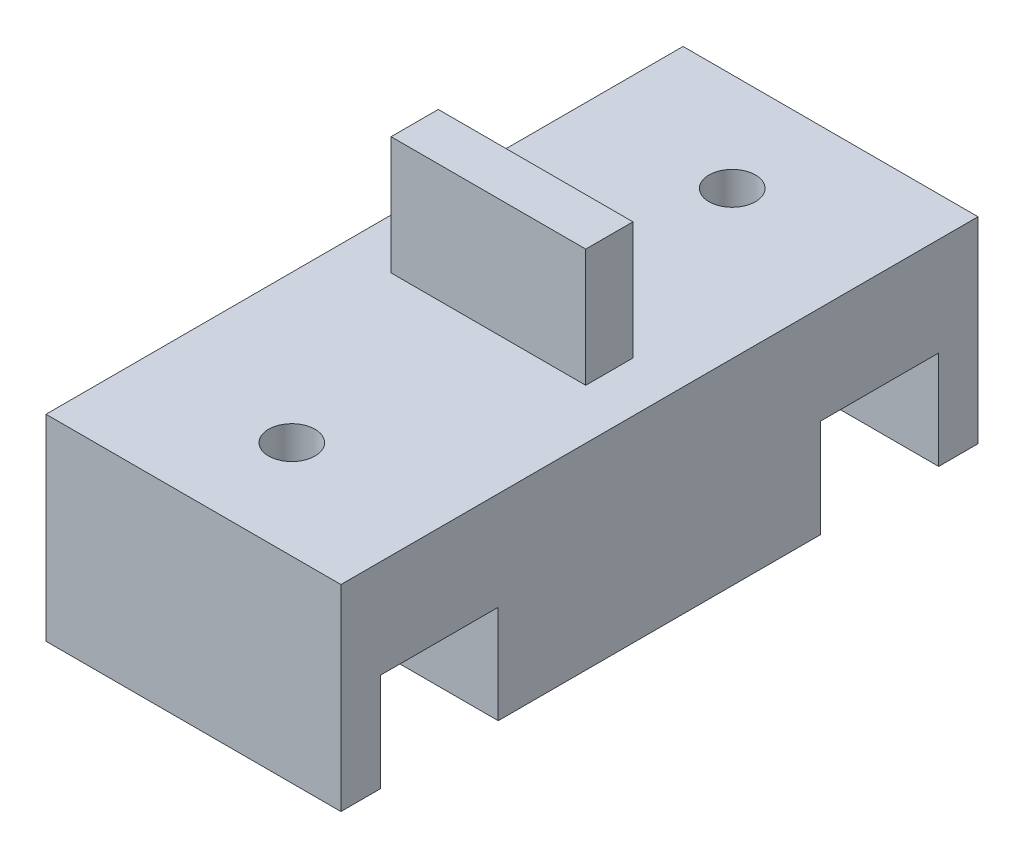
SolidWorks part; units mm, degrees
ref_plane "Front Plane" through (0, 0, 0) normal (0, 0, 1) x (1, 0, 0)
ref_plane "Top Plane" through (0, 0, 0) normal (0, 1, 0) x (1, 0, 0)
ref_plane "Right Plane" through (0, 0, 0) normal (1, 0, 0) x (0, 0, -1)
sketch "Sketch1" plane through (0, 0, 0) normal (1, 0, 0) x (0, 0, -1)
  line L1 (-20.574, 12.7) -> (20.574, 12.7)
  line L2 (-20.574, 12.7) -> (-20.574, 0)
  line L3 (-20.574, 0) -> (20.574, 0)
  line L4 (20.574, 12.7) -> (20.574, 0)
  line L5 (-1.524, 12.7) -> (1.524, 12.7)
  line L6 (-1.524, 12.7) -> (-1.524, 20.32)
  line L7 (-1.524, 20.32) -> (1.524, 20.32)
  line L8 (1.524, 12.7) -> (1.524, 20.32)
  point P10 (0, 20.32)
  point P14 (0, 0)
  dimension "D1" = 12.7
  dimension "D2" = 7.62
  dimension "D3" = 3.048
  dimension "D4" = 19.05
extrude "Boss-Extrude1" add sketch "Sketch1" along normal mid plane 19.05 contours L4 L1 L2 L3 region at (0, 6.35, 0)
extrude "Boss-Extrude2" add sketch "Sketch1<3>" along normal mid plane 12.573 contours L1 L8 L7 L6 region at (0, 16.51, 0)
sketch "Sketch1<3>" plane through (0, 0, 0) normal (1, 0, 0) x (0, 0, -1) same geometry as "Sketch1"
sketch "Sketch2" plane through (0, 0, 1.524) normal (0, 0, 1) x (1, 0, 0)
  line L0 (-6.2865, 19.05) -> (6.2865, 19.05) construction
  line L1 (-6.2865, 12.7) -> (-6.2865, 20.32) construction
  line L2 (6.2865, 12.7) -> (6.2865, 20.32) construction
  line L3 (9.525, 12.7) -> (-9.525, 12.7) construction
  circle A0 centre (0, 31.75) radius 1.5
  point P11 (0, 19.05)
  dimension "D3" = 3
  dimension "D1" = 6.35
  dimension "D2" = 12.7
extrude "Cut-Extrude1" [suppressed] cut sketch "Sketch2" against normal through all
sketch "Sketch4" plane through (0, 12.7, 0) normal (0, 1, 0) x (1, 0, 0)
  line L0 (0, -14.224) -> (0, 14.224) construction
  line L1 (6.2865, -1.524) -> (-6.2865, -1.524) construction
  circle A0 centre (0, -14.224) radius 1.5
  circle A2 centre (0, 14.224) radius 1.5
  point P2 (0, 0)
  dimension "D1" = 3
  dimension "D2" = 12.7
extrude "Cut-Extrude3" cut sketch "Sketch4" against normal through all
sketch "Sketch5" plane through (0, 0, 0) normal (0, -1, 0) x (1, 0, 0)
  line L0 (9.525, -18.034) -> (-9.525, -18.034)
  line L1 (9.525, 20.574) -> (9.525, -20.574) construction
  line L2 (-9.525, 20.574) -> (-9.525, -20.574) construction
  line L3 (-9.525, -18.034) -> (-9.525, -10.414)
  line L4 (-9.525, -10.414) -> (9.525, -10.414)
  line L5 (9.525, -10.414) -> (9.525, -18.034)
  line L6 (-9.525, 10.414) -> (9.525, 10.414)
  line L7 (9.525, 10.414) -> (9.525, 18.034)
  line L8 (9.525, 18.034) -> (-9.525, 18.034)
  line L9 (-9.525, 18.034) -> (-9.525, 10.414)
  circle A0 centre (0, 14.224) radius 3.81
  circle A1 centre (0, -14.224) radius 3.81
  circle A2 centre (0, 14.224) radius 1.5 construction
  circle A3 centre (0, -14.224) radius 1.5 construction
  circle M7 centre (0, 14.224) radius 1.5
  circle M8 centre (0, -14.224) radius 1.5
  line M9 (-9.525, 20.574) -> (-9.525, -20.574)
  line M11 (9.525, -20.574) -> (9.525, 20.574)
  dimension "D1" = 7.62
extrude "Cut-Extrude4" cut sketch "Sketch5" against normal blind 6.35 contours A1 L4 L0 M9 | A1 M8 | A1 L0 L4 M11 | A0 L6 L8 M11 | A0 M7 | A0 L8 L6 M9 region at (6.2033, 0, -14.224) region at (-6.2033, 0, -14.224) region at (-3.7022, 0, -14.224) region at (6.2033, 0, 14.224) region at (-6.2033, 0, 14.224) region at (-3.7022, 0, 14.224)
